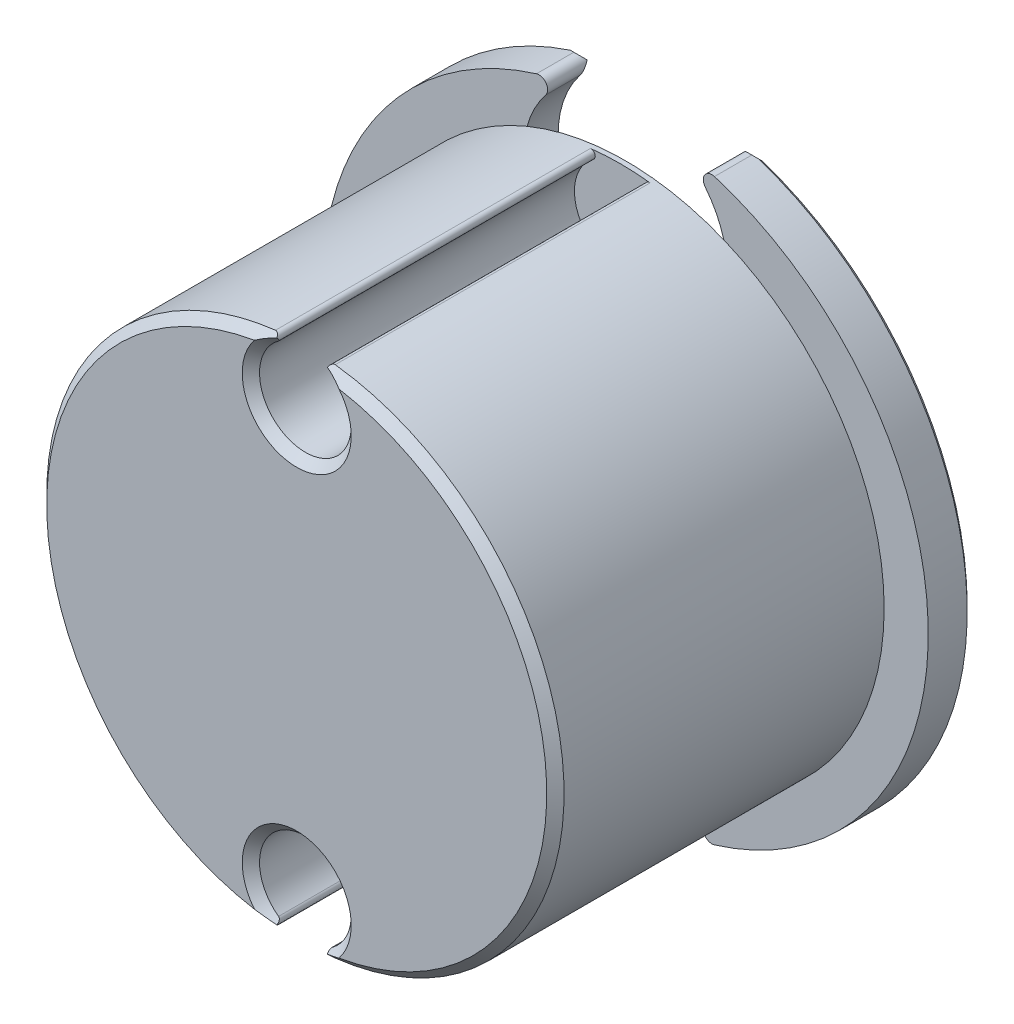
SolidWorks part; units mm, degrees
ref_plane "Front Plane" through (0, 0, 0) normal (0, 0, 1) x (1, 0, 0)
ref_plane "Top Plane" through (0, 0, 0) normal (0, 1, 0) x (1, 0, 0)
ref_plane "Right Plane" through (0, 0, 0) normal (1, 0, 0) x (0, 0, -1)
sketch "Sketch2" plane through (0, 0, 0) normal (0, 0, 1) x (1, 0, 0)
  line L0 (0, 20.6512) -> (0, 0) construction
  line L1 (0, 0) -> (19.945, 0) construction
  arc A0 (-0.4804, 14.9423) -> (-0.4804, -14.9423) centre (0, 0) ccw
  arc A4 (0, 14.95) -> (-0.4804, 14.9423) centre (0, 0) ccw construction
  arc A6 (0.4804, 14.9423) -> (0, 14.95) centre (0, 0) ccw construction
  arc A8 (0.4804, -14.9423) -> (0.4804, 14.9423) centre (0, 0) ccw
  arc A11 (-0.1409, 14.8963) -> (0.1409, 14.8963) centre (0, 12.25) ccw
  arc A12 (0.4804, 14.9423) -> (0.1409, 14.8963) centre (0.4472, 13.9118) ccw
  arc A13 (-0.4804, 14.9423) -> (-0.1409, 14.8963) centre (-0.4472, 13.9118) cw
  arc A14 (-0.1409, -14.8963) -> (0.1409, -14.8963) centre (0, -12.25) cw
  arc A15 (0.4804, -14.9423) -> (0.1409, -14.8963) centre (0.4472, -13.9118) cw
  arc A16 (-0.4804, -14.9423) -> (-0.1409, -14.8963) centre (-0.4472, -13.9118) ccw
  dimension "D1" = 29.9
  dimension "D4" = 5.3
  dimension "D5" = 24.5
extrude "Boss-Extrude1" add sketch "Sketch2" along normal blind 19
fillet "Fillet2" radius 0.25 4 edges at (0.1409, 14.8963, 9.5) (-0.1409, 14.8963, 9.5) (0.1409, -14.8963, 9.5) (-0.1409, -14.8963, 9.5)
sketch "Sketch3" plane through (0, 0, 0) normal (0, 0, -1) x (-1, 0, 0)
  circle A0 centre (0, 0) radius 17.5
  circle A1 centre (0, 12.25) radius 2.65
  circle A2 centre (0, -12.25) radius 2.65
  arc A5 (1.5506, -14.399) -> (-1.5506, -14.399) centre (0, -12.25) ccw construction
  arc A6 (-1.5506, 14.399) -> (1.5506, 14.399) centre (0, 12.25) ccw construction
  dimension "D1" = 35
extrude "Boss-Extrude2" add sketch "Sketch3" along normal blind 2.5
sketch "Sketch4" plane through (0, 0, -2.5) normal (0, 0, -1) x (-1, 0, 0)
  circle A0 centre (0, 12.25) radius 5.9
  circle A1 centre (0, -12.25) radius 5.9
  dimension "D1" = 11.8
extrude "Cut-Extrude1" cut sketch "Sketch4" against normal up to surface (2.5 mm away) up to face at (-17.5, 0, 0)
fillet "Fillet1" radius 0.5 4 edges at (-3.2041, -17.2042, -1.25) (3.2041, -17.2042, -1.25) (3.2041, 17.2042, -1.25) (-3.2041, 17.2042, -1.25)
sketch "Sketch6" plane through (0, 0, 0) normal (1, 0, 0) x (0, 0, -1)
  line L0 (2.5, 16.3848) -> (1.839, 17.0457)
  line L1 (2.5, -17.5) -> (2.5, 17.5) construction
  line L2 (2.5, 16.3848) -> (2.5, 17.0457)
  line L3 (2.5, 17.0457) -> (1.839, 17.0457)
  line L4 (0, 0) -> (7.9617, 0) construction
  line L5 (2.5, -17.0457) -> (1.839, -17.0457)
  line L6 (2.5, -16.3848) -> (2.5, -17.0457)
  line L7 (2.5, -16.3848) -> (1.839, -17.0457)
  dimension "D1" = 45
extrude "Cut-Extrude2" cut sketch "Sketch6" against normal through all and the other way through all
sketch "Sketch5" plane through (0, 0, 0) normal (0, 0, -1) x (-1, 0, 0)
  line L0 (1.7257, 14.8501) -> (3.5997, 11.6681)
  line L1 (3.5997, 11.6681) -> (0.3325, 8.7199)
  line L2 (0.3325, 8.7199) -> (-3.5865, 11.0834)
  line L3 (-3.5865, 11.0834) -> (-1.7257, 14.8501)
  line L4 (0, 0) -> (9.4104, 0) construction
  line L5 (-3.5865, -11.0834) -> (-1.7257, -14.8501)
  line L6 (0.3325, -8.7199) -> (-3.5865, -11.0834)
  line L7 (3.5997, -11.6681) -> (0.3325, -8.7199)
  line L8 (1.7257, -14.8501) -> (3.5997, -11.6681)
  arc A3 (-1.7257, 14.8501) -> (1.7257, 14.8501) centre (0, 0) cw
  arc A6 (5.6854, 13.8267) -> (1.7257, 14.8501) centre (0, 0) ccw construction
  arc A8 (-1.7257, -14.8501) -> (1.7257, -14.8501) centre (0, 0) ccw
extrude "Boss-Extrude3" add sketch "Sketch5" against normal blind 0.3
sketch "Sketch7" plane through (0, 0, 0) normal (0, 1, 0) x (1, 0, 0)
  line L0 (17.5, 0.4) -> (15.4, 2.5)
  line L1 (17.5, 0) -> (17.5, 2.5) construction
  line L2 (17.5, 2.5) -> (6.1473, 2.5) construction
  line L3 (15.4, 2.5) -> (17.5, 2.5)
  line L4 (17.5, 2.5) -> (17.5, 0.4)
  line L5 (5.1437, 0) -> (17.5, 0) construction
  line L6 (0, 0) -> (0, 5.7107) construction
  line L7 (-17.5, 2.5) -> (-17.5, 0.4)
  line L8 (-15.4, 2.5) -> (-17.5, 2.5)
  line L9 (-17.5, 0.4) -> (-15.4, 2.5)
  dimension "D1" = 45
  dimension "D2" = 0.4
extrude "Cut-Extrude3" [suppressed] cut sketch "Sketch7" against normal through all and the other way through all
chamfer "Chamfer1" distance 0.25 angle 45 2 edges at (-17.5, 0, -2.5) (17.5, 0, -2.5)
chamfer "Chamfer2" distance 0.5 angle 45 6 edges at (0, -6.35, -2.5) (0, 6.35, -2.5) (0, -9.6, 19) (0, 9.6, 19) (-14.95, 0, 19) (14.95, 0, 19)
